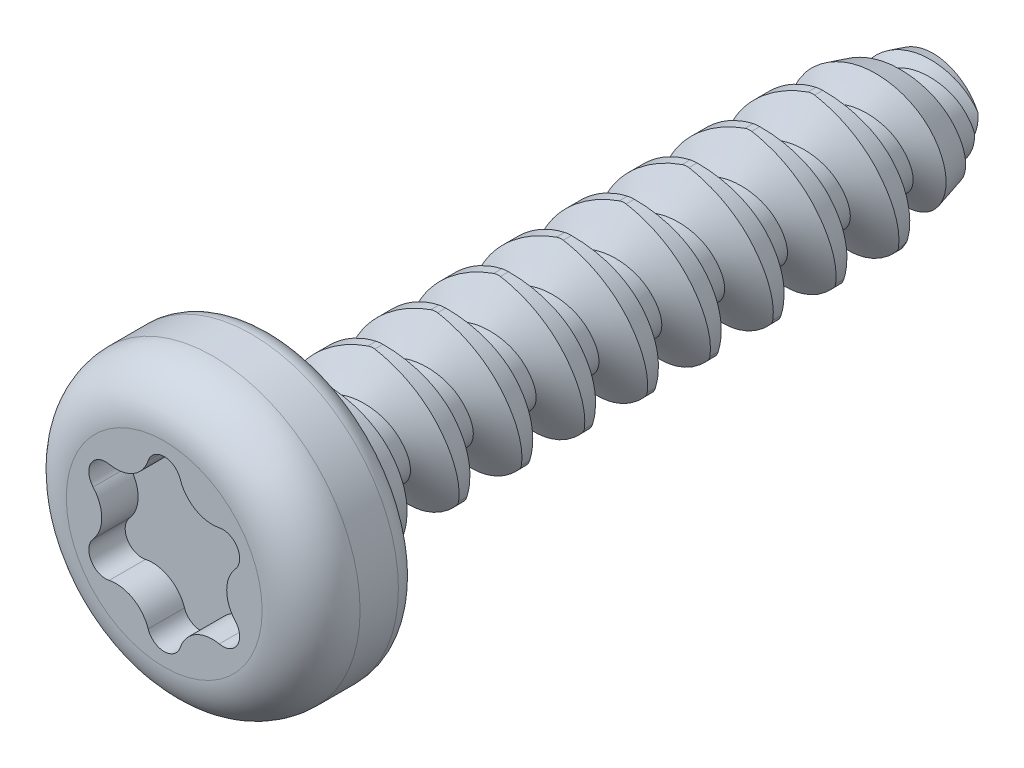
SolidWorks part; units mm, degrees
note: '?' marks a value the reader was unsure of.
ref_plane "Front" through (0, 0, 0) normal (0, 0, 1) x (1, 0, 0)
ref_plane "Top" through (0, 0, 0) normal (0, 1, 0) x (1, 0, 0)
ref_plane "Right" through (0, 0, 0) normal (1, 0, 0) x (0, 0, -1)
sketch "Sketch1" plane through (0, 0, 0) normal (0, 0, 1) x (1, 0, 0)
  circle A0 centre (0, 0) radius 2.1209
  dimension "Head Dia" = 4.2418
extrude "Extrude3" add sketch "Sketch1" along normal blind 1.5748
ref_plane "Plane1" through (0, 0, 1.5748) normal (0, 0, 1) x (1, 0, 0)
sketch "Sketch11" plane through (0, 0, 0) normal (1, 0, 0) x (0, 0, -1)
  line L2 (-1.5748, 2.1209) -> (-1.5748, -2.1209) construction
  line L4 (0, 2.1209) -> (-1.5748, 2.1209) construction
  line L5 (-0.8678, 2.1209) -> (-0.315, 2.1209)
  line L6 (0, -2.1209) -> (0, 2.1209) construction
  line L7 (-1.5748, 2.1209) -> (-1.5748, 1.4139) construction
  line L8 (-1.5748, 0.707) -> (-1.5748, 0) construction
  line L9 (-1.5748, 1.4139) -> (-1.5748, 0.707) construction
  line L10 (-1.5748, 1.4139) -> (-1.8288, 1.4139)
  line L11 (0, 0) -> (-1.5748, 0) construction
  line L12 (-1.8288, 1.4139) -> (-1.8288, 2.3749)
  line L13 (-1.8288, 2.3749) -> (0.254, 2.3749)
  line L14 (0.254, 2.3749) -> (0.254, 1.8059)
  line L15 (0.254, 1.8059) -> (0, 1.8059)
  arc A0 (-1.5748, 1.4139) -> (-0.8678, 2.1209) centre (-0.8678, 1.4139) cw
  arc A1 (-0.315, 2.1209) -> (0, 1.8059) centre (-0.315, 1.8059) cw
  dimension "D1" = 0.315
  dimension "D2" = 0.254
  dimension "D3" = 0.254
revolve "Cut-Revolve3" cut sketch "Sketch11" angle 360 about L11
sketch "Sketch14" plane through (0, 0, 0) normal (1, 0, 0) x (0, 0, -1)
  line L0 (0.2268, 0.6012) -> (0.5103, 1.0922) construction
  line L2 (0.5103, 1.0922) -> (0.6237, 1.0922)
  line L3 (0.6237, 1.0922) -> (0.9071, 0.6012) construction
  line L4 (0.9071, 0.6012) -> (0.2268, 0.6012) construction
  line L5 (0.9071, 0.6012) -> (1.1339, 0.6012) construction
  line L6 (0.2268, 0.6012) -> (0, 0.6012) construction
  line L10 (0, 2.1209) -> (0, -2.1209) construction
  line L11 (0.5103, 1.0922) -> (0.2268, 0.6012)
  line L12 (0.2268, 0.6012) -> (0.9071, 0.6012)
  line L13 (0.9071, 0.6012) -> (0.6237, 1.0922)
  line L14 (0, 0) -> (-1.5748, 0) construction
  line L15 (0, 0) -> (-1.5748, 0) construction
  point P11 (0.567, 1.0922)
  dimension "D1" = 60
  dimension "Pitch" = 0.9071
  dimension "D3" = 0.2268
  dimension "D4" = 0.1134
  dimension "Screw Dia" = 2.1844
ref_plane "Plane2" through (0, 0, -0.567) normal (0, 0, 1) x (1, 0, 0)
sketch "Sketch15" plane through (0, 0, -0.567) normal (0, 0, 1) x (1, 0, 0)
  circle A0 centre (0, 0) radius 1.0922
curve "Helix/Spiral1" pitch 0.9071 height 1.3607 turns 1.5
sketch "Sketch17" plane through (0, 0, 0) normal (1, 0, 0) x (0, 0, -1)
  line L1 (0, 0) -> (9.525, 0)
  line L2 (0, 0) -> (0, 0.6012)
  line L3 (0, 0.6012) -> (9.525, 0.6012)
  line L4 (9.525, 0) -> (9.525, 0.6012)
  dimension "Body Length" = 9.525
revolve "Revolve1" add sketch "Sketch17" angle 360 about L11
sweep "Sweep1" add profiles "Sketch14" path "Helix/Spiral1"
pattern_linear "LPattern3" count 10 spacing 0.9071 along (0, 0, -1) count 2 spacing 0.9071 along (0, 0, 1) of "Sweep1"
sketch "Sketch13" plane through (0, 0, 0) normal (1, 0, 0) x (0, 0, -1)
  line L0 (9.525, 0.7112) -> (8.1407, 1.0922)
  line L2 (8.1407, 1.0922) -> (9.525, 1.0922)
  line L3 (9.525, 1.0922) -> (9.525, 0.7112) construction
  line L4 (9.525, 0.7112) -> (9.525, 0)
  line L5 (0, 0) -> (9.525, 0) construction
  line L6 (0.5103, 1.0922) -> (0.6237, 1.0922) construction
  line L7 (12.065, 0) -> (12.065, 1.0922)
  line L8 (12.065, 1.0922) -> (9.525, 1.0922)
  line L9 (9.525, 0) -> (12.065, 0)
  dimension "D3" = 2.54
  dimension "Point Dia" = 1.4224
  dimension "Point Lg" = 1.3843
revolve "Cut-Revolve4" cut sketch "Sketch13" angle 360 about L5
sketch "Sketch12" plane through (0, 0, 1.5748) normal (0, 0, 1) x (1, 0, 0)
  line L0 (0, 0) -> (0, 1.2192) construction
  line L1 (0, 0) -> (0.4511, 0.7814) construction
  line L2 (0, 0) -> (-0.4511, 0.7814) construction
  line L3 (-0.4511, 0.7814) -> (0, 0)
  line L4 (0, 0) -> (0.4511, 0.7814)
  arc A0 (-0.4511, 0.7814) -> (-0.2317, 1.0515) centre (-0.695, 1.2037) ccw
  arc A1 (-0.2317, 1.0515) -> (0.2317, 1.0515) centre (0, 0.9754) cw
  arc A2 (0.2317, 1.0515) -> (0.4511, 0.7814) centre (0.695, 1.2037) ccw
  circle A5 centre (0, 0) radius 1.2192 construction
  dimension "D1" = 60
  dimension "M" = 2.4384
  dimension "D2" = 0.2438
  dimension "D3" = 0.4877
extrude "Cut-Extrude1" cut sketch "Sketch12" against normal blind 0.5249
ref_axis "Axis1" through (0, 0, 1.5748) along (0, 0, -1)?
pattern_circular "CirPattern1" count 6 every 60 about axis through (0, 0, 0) along (0, 0, 1) of "Cut-Extrude1"
sketch "Sketch18" plane through (0, 0, -9.525) normal (0, 0, -1) x (-1, 0, 0)
  line L0 (0, 1.0922) -> (0, 0) construction
  line L1 (0, 0) -> (-0.9459, -0.5461) construction
  line L2 (0, 0) -> (0.9459, -0.5461) construction
  circle A0 centre (0, 0) radius 1.0922 construction
  arc A1 (-0.0435, 1.0878) -> (0.0435, 1.0878) centre (0, 0.8738) cw
  arc A2 (-0.9638, -0.5062) -> (-0.9203, -0.5816) centre (-0.7567, -0.4369) ccw
  arc A3 (0.9638, -0.5062) -> (0.9203, -0.5816) centre (0.7567, -0.4369) cw
  arc A4 (-0.0435, 1.0878) -> (-0.9638, -0.5062) centre (0.2014, -0.1163) ccw
  arc A5 (0.0435, 1.0878) -> (0.9638, -0.5062) centre (-0.2014, -0.1163) cw
  arc A6 (-0.9203, -0.5816) -> (0.9203, -0.5816) centre (0, 0.2325) ccw
  dimension "D3" = 0.2184
  dimension "D4" = 1.2287
  dimension "D1" = 120
  dimension "D2" = 120
extrude "Cut-Extrude3" cut sketch "Sketch18" against normal up to surface (9.525 mm away) flip side to cut up to face at (-1.8059, 0, 0)
equation "\"D3@LPattern3\"=\"Pitch@Sketch14\""
equation "\"D1@LPattern3\"=(\"Body Length@Sketch17\"/\"Pitch@Sketch14\")-1"
equation "\"D1@Cut-Extrude1\"=\"Head Ht@Extrude3\"/3"
equation "\"D3@Sketch14\" = \"Pitch@Sketch14\"/4"
equation "\"D4@Sketch14\" = \"Pitch@Sketch14\"/8"
equation "\"D4@LPattern3\" = \"D3@LPattern3\""
equation "\"D4@Helix/Spiral1\" = \"Pitch@Sketch14\""
equation "\"D2@Sketch12\" = \"M@Sketch12\"*.1"
equation "\"D3@Sketch12\" = \"D2@Sketch12\"*2"
equation "\"D3@Sketch18\" = \"Screw Dia@Sketch14\"*.1"
equation "\"D4@Sketch18\" = \"Screw Dia@Sketch14\"*.5625"
equation "\"D1@Sketch11\" = \"Head Ht@Extrude3\"/5"
